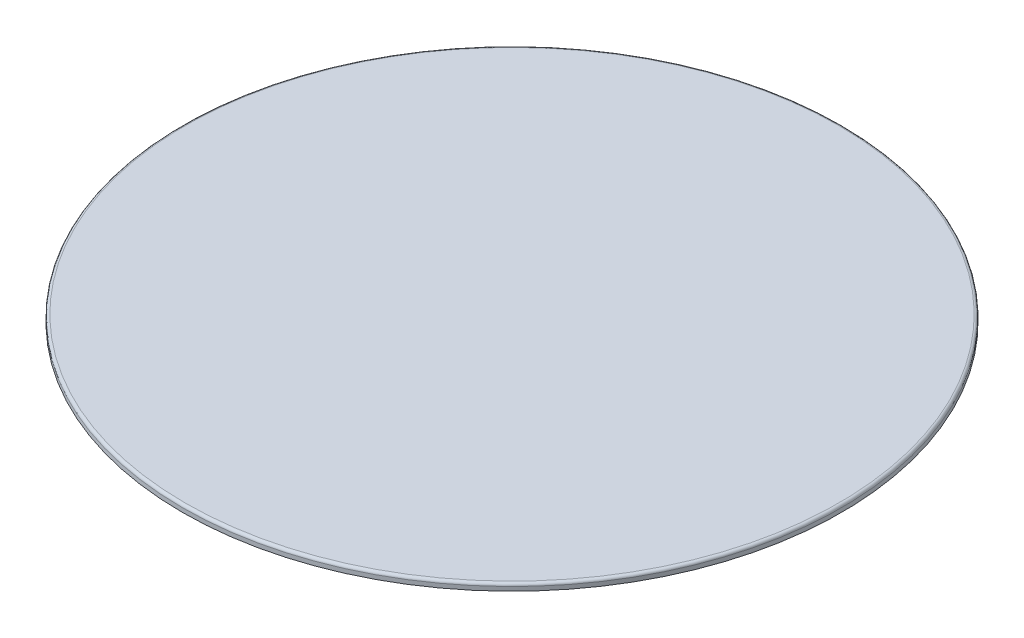
SolidWorks part; units mm, degrees
material "POLYURETHANE (11671)"
ref_plane "Front Plane" through (0, 0, 0) normal (0, 0, 1) x (1, 0, 0)
ref_plane "Top Plane" through (0, 0, 0) normal (0, 1, 0) x (1, 0, 0)
ref_plane "Right Plane" through (0, 0, 0) normal (1, 0, 0) x (0, 0, -1)
ref_axis "CentralAxis" through (0, 0.525, 0) along (0, -1, 0)
sketch "BaseS" plane through (0, 0, 0) normal (0, 1, 0) x (1, 0, 0)
  circle A0 centre (0, 0) radius 24.1
  dimension "Diameter" = 48.2
extrude "Base" add sketch "BaseS" along normal blind 0.5
fillet "BaseFillet" radius 0.2 1 edges at (0, 0.5, 24.1)
